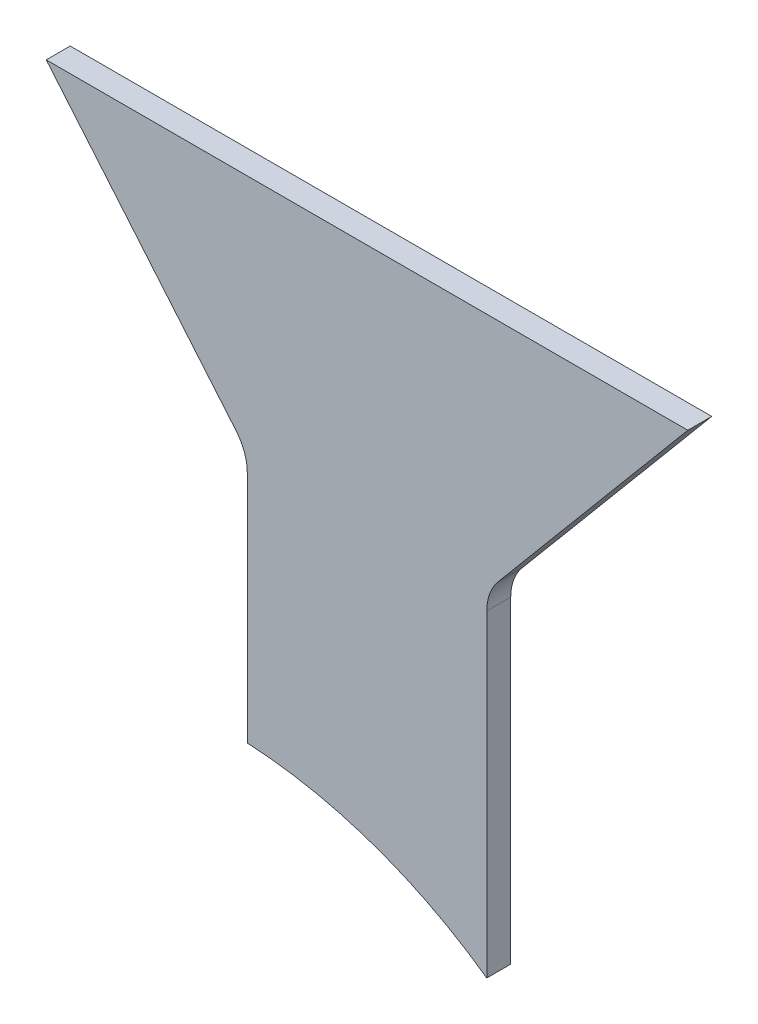
SolidWorks part; units mm, degrees
material "201 Annealed Stainless Steel (SS)"
ref_plane "Front Plane" through (0, 0, 0) normal (0, 0, 1) x (1, 0, 0)
ref_plane "Top Plane" through (0, 0, 0) normal (0, 1, 0) x (1, 0, 0)
ref_plane "Right Plane" through (0, 0, 0) normal (1, 0, 0) x (0, 0, -1)
sketch "Sketch1" plane through (0, 0, 0) normal (0, 0, 1) x (1, 0, 0)
  line L1 (25, 0) -> (25, 70)
  line L2 (25, 70) -> (66.974, 120.0227)
  line L6 (0, 0) -> (25, 0) construction
  line L7 (0, 0) -> (0, 120.0227) construction
  line L8 (-66.974, 120.0227) -> (66.974, 120.0227)
  line L9 (-25, 17.5) -> (-25, 70)
  line L10 (-25, 70) -> (-66.974, 120.0227)
  line L11 (0, 0) -> (0, -123.071) construction
  line L12 (-30.1388, -77.3609) -> (52.4872, -77.3609) construction
  line L13 (-25, 0) -> (-25, 17.5) construction
  line L14 (-25, 0) -> (0, 0) construction
  line L15 (-25, 17.5) -> (-25, -94.1356) construction
  line L16 (25, 0) -> (25, -97.0815) construction
  arc A1 (25, 0) -> (-25, 17.5) centre (-30.1388, -77.3609) ccw
  circle A2 centre (-30.1388, -77.3609) radius 95 construction
  dimension "D5" = 95
  dimension "D6" = 52.5
  dimension "D1" = 25
  dimension "D2" = 140
  dimension "D3" = 65.3
  dimension "D4" = 70
extrude "Funnel - Side Panel" add sketch "Sketch1" along normal blind 5
fillet "Fillet1" radius 10 2 edges at (-25, 70, 2.5) (25, 70, 2.5)
